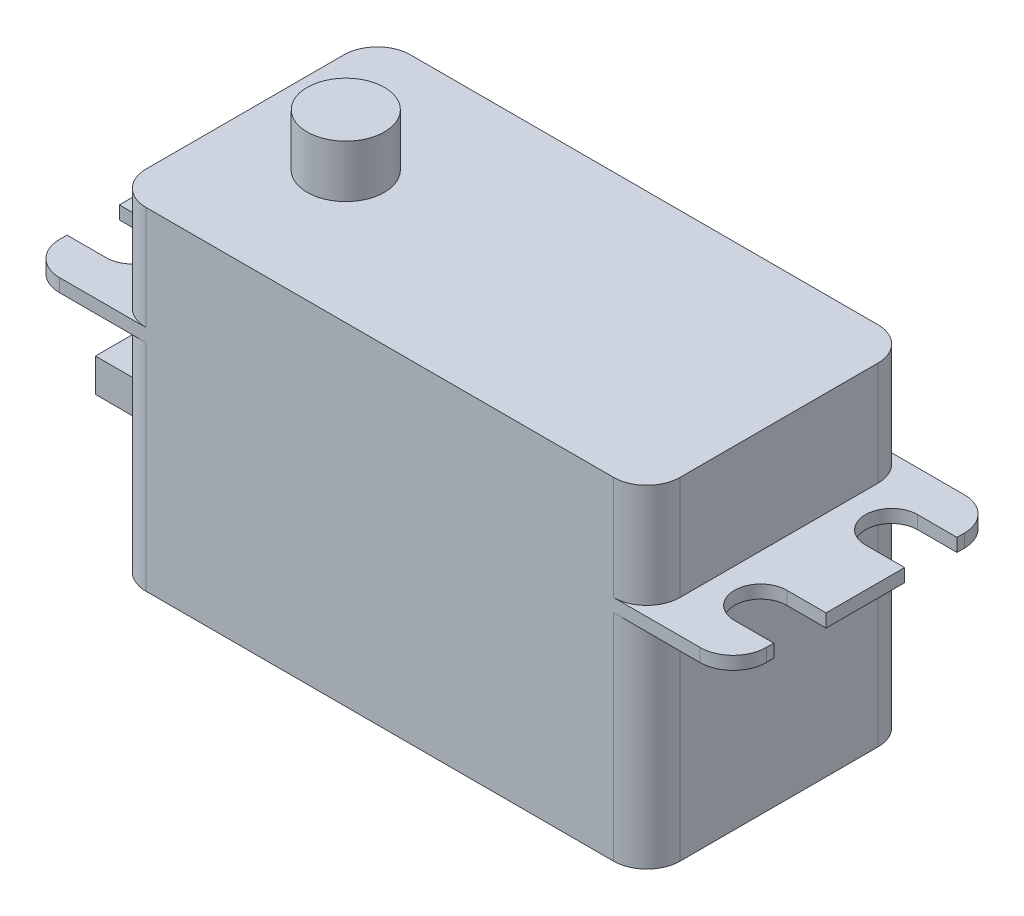
SolidWorks part; units mm, degrees
ref_plane "Front Plane" through (0, 0, 0) normal (0, 0, 1) x (1, 0, 0)
ref_plane "Top Plane" through (0, 0, 0) normal (0, 1, 0) x (1, 0, 0)
ref_plane "Right Plane" through (0, 0, 0) normal (1, 0, 0) x (0, 0, -1)
sketch "Sketch1" plane through (0, 0, 0) normal (0, 1, 0) x (1, 0, 0)
  line L0 (-16.17, 0) -> (16.17, 0) construction
  line L1 (-24.46, -10.1) -> (24.46, -10.1)
  line L2 (-27, -7.56) -> (-27, 7.56)
  line L3 (-24.46, 10.1) -> (24.46, 10.1)
  line L4 (27, -7.56) -> (27, 7.56)
  line L5 (-27, -10.1) -> (27, 10.1) construction
  line L6 (-27, 10.1) -> (27, -10.1) construction
  line L7 (0, -11.11) -> (0, 11.11) construction
  line L8 (24, 3) -> (27, 3)
  line L9 (24, 7) -> (27, 7)
  line L10 (27, 7) -> (27, 3)
  line L11 (24, -3) -> (27, -3)
  line L12 (24, -7) -> (27, -7)
  line L13 (27, -7) -> (27, -3)
  line L14 (-24, 7) -> (-27, 7)
  line L15 (-24, 3) -> (-27, 3)
  line L16 (-27, 3) -> (-27, 7)
  line L17 (-24, -7) -> (-27, -7)
  line L18 (-24, -3) -> (-27, -3)
  line L19 (-27, -3) -> (-27, -7)
  arc A0 (24, 7) -> (24, 3) centre (24, 5) ccw
  arc A1 (24, -7) -> (24, -3) centre (24, -5) cw
  arc A2 (-24, -7) -> (-24, -3) centre (-24, -5) ccw
  arc A3 (-24, 7) -> (-24, 3) centre (-24, 5) cw
  arc A4 (-24.46, -10.1) -> (-27, -7.56) centre (-24.46, -7.56) cw
  arc A5 (24.46, -10.1) -> (27, -7.56) centre (24.46, -7.56) ccw
  arc A6 (24.46, 10.1) -> (27, 7.56) centre (24.46, 7.56) cw
  arc A7 (-27, 7.56) -> (-24.46, 10.1) centre (-24.46, 7.56) cw
  point P0 (0, 0)
  dimension "D3" = 4
  dimension "D6" = 2.54
  dimension "D1" = 54
  dimension "D2" = 20.2
  dimension "D4" = 48
  dimension "D5" = 10
extrude "Boss-Extrude1" add sketch "Sketch1" along normal blind 1 contours A7 L2 L14 A3 L15 L18 A2 L17 A4 L1 A5 L4 L12 A1 L11 L8 A0 L9 A6 L3 region at (0, 0, 0)
sketch "Sketch3" plane through (0, 1, 0) normal (0, 1, 0) x (1, 0, 0)
  line L1 (-17.86, -10.1) -> (17.86, -10.1)
  line L2 (-20.4, -7.56) -> (-20.4, 7.56)
  line L3 (-17.86, 10.1) -> (17.86, 10.1)
  line L4 (20.4, -7.56) -> (20.4, 7.56)
  line L5 (-20.4, -10.1) -> (20.4, 10.1) construction
  line L6 (-20.4, 10.1) -> (20.4, -10.1) construction
  arc A0 (-17.86, -10.1) -> (-20.4, -7.56) centre (-17.86, -7.56) cw
  arc A1 (17.86, -10.1) -> (20.4, -7.56) centre (17.86, -7.56) ccw
  arc A2 (17.86, 10.1) -> (20.4, 7.56) centre (17.86, 7.56) cw
  arc A3 (-20.4, 7.56) -> (-17.86, 10.1) centre (-17.86, 7.56) cw
  point P0 (0, 0)
  dimension "D3" = 2.54
  dimension "D1" = 40.8
  dimension "D2" = 20.2
extrude "Boss-Extrude2" add sketch "Sketch3" along normal blind 7.95
sketch "Sketch4" plane through (0, 0, 0) normal (0, -1, 0) x (1, 0, 0)
  line L1 (-17.86, -10.1) -> (17.86, -10.1)
  line L2 (-20.4, -7.56) -> (-20.4, 7.56)
  line L3 (-17.86, 10.1) -> (17.86, 10.1)
  line L4 (20.4, -7.56) -> (20.4, 7.56)
  line L5 (-20.4, -10.1) -> (20.4, 10.1) construction
  line L6 (-20.4, 10.1) -> (20.4, -10.1) construction
  arc A0 (-17.86, -10.1) -> (-20.4, -7.56) centre (-17.86, -7.56) cw
  arc A1 (17.86, -10.1) -> (20.4, -7.56) centre (17.86, -7.56) ccw
  arc A2 (17.86, 10.1) -> (20.4, 7.56) centre (17.86, 7.56) cw
  arc A3 (-20.4, 7.56) -> (-17.86, 10.1) centre (-17.86, 7.56) cw
  point P0 (0, 0)
  dimension "D3" = 2.54
  dimension "D1" = 20.2
  dimension "D2" = 40.8
extrude "Boss-Extrude3" add sketch "Sketch4" along normal blind 16.45
sketch "Sketch5" plane through (-20.4, 0, 0) normal (-1, 0, 0) x (0, 0, 1)
  line L0 (-0.8843, -9.5287) -> (-0.8843, -11.2259)
  line L1 (-3.81, -11.6473) -> (3.81, -11.6473)
  line L2 (-3.81, -11.6473) -> (-3.81, -9.1073)
  line L3 (-3.81, -9.1073) -> (3.81, -9.1073)
  line L4 (3.81, -11.6473) -> (3.81, -9.1073)
  line L5 (-3.4243, -9.5287) -> (-1.6557, -9.5287)
  line L6 (-3.4243, -9.5287) -> (-3.4243, -11.2259)
  line L7 (-3.4243, -11.2259) -> (-1.6557, -11.2259)
  line L8 (-1.6557, -9.5287) -> (-1.6557, -11.2259)
  line L9 (-0.8843, -9.5287) -> (0.8843, -9.5287)
  line L10 (0.8843, -9.5287) -> (0.8843, -11.2259)
  line L11 (-0.8843, -11.2259) -> (0.8843, -11.2259)
  line L12 (1.6557, -9.5287) -> (1.6557, -11.2259)
  line L13 (1.6557, -9.5287) -> (3.4243, -9.5287)
  line L14 (3.4243, -9.5287) -> (3.4243, -11.2259)
  line L15 (1.6557, -11.2259) -> (3.4243, -11.2259)
  point P8 (0, -11.6473)
  point P18 (-3.4243, -10.3773)
  point P19 (-3.81, -10.3773)
  point P20 (0, -11.2259)
  dimension "D2" = 2.54
  dimension "D3" = 2.54
  dimension "D4" = 7.62
  dimension "D1" = 3
extrude "Boss-Extrude4" add sketch "Sketch5" along normal blind 7.62
sketch "Sketch6" plane through (0, 8.95, 0) normal (0, 1, 0) x (1, 0, 0)
  circle A0 centre (-12.7, 0) radius 2.95
  dimension "D1" = 5.9
  dimension "D2" = 12.7
extrude "Boss-Extrude5" add sketch "Sketch6" along normal blind 4
other "CPoint1"
ref_axis "Axis1" through (-38.02, -11.2259, -3.4243) along (1, 0, 0)
other "CPoint2"
ref_axis "Axis2" through (-38.02, -11.2259, -0.8843) along (1, 0, 0)
other "CPoint3"
ref_axis "Axis3" through (-38.02, -11.2259, 1.6557) along (1, 0, 0)
equation "\"Bodytube_OD\" = 6.17in"
equation "\"Bodytube_ID\" = 5.998in"
equation "\"Motor_OD\" = 4in"
equation "\"Fwd_Tube_Length\" = 40in"
equation "\"Mid_Tube_Length\" = 1in"
equation "\"Aft_Section_Length\"= 39in"
equation "\"AB_Coupler_OD_Length\"= 1in"
equation "\"AB_Coupling_Section_Length\"= 0.375in"
equation "\"AB_Coupler_Length\"= \"AB_Coupler_OD_Length\" + \"AB_Coupling_Section_Length\" * 2"
equation "\"Cutout_Angle\" = 80"
equation "\"AB_Paddle_Height\" = 0.375in"
equation "\"AB_Coupler_Num_Screws\"= 6"
equation "\"Num_Cutouts\" = 3"
equation "\"AB_Coupler_OD\"= 6.17in"
equation "\"AB_Coupler_ID\"= 5.75in"
equation "\"AB_Coupler_Surface_Diameter\"= 5.998in"
equation "\"AB_Coupling_Screw_Diameter\"= 0.1065in"
equation "\"AB_Central_Bushing_Length\" = .75in"
equation "\"Lead_Screw_Dist\" = 2.25in"
equation "\"Lead_Screw_Diam\" = 11mm"
equation "\"Paddle_Pin_Offset\" = .25in"
equation "\"Paddle_Pin_Radius\" = 2.25in"
equation "\"Paddle_Gear_OD\" = 3.2in"
equation "\"Drive_Gear_OD\" = 1.7in"
equation "\"Fwd_BKHD_From_Top\" = 18in"
equation "\"Fin_Thickness\"= .118in"
equation "\"Guiderail_Cutout_Diameter\"= 1.5in"
equation "\"DB9_Hole_Dist\" = 25mm"
equation "\"Airbrakes_Wire_Hole_Dia\" = .25in"
equation "\"Airbrakes_Wire_Hole_Dist\" = 1.1in"
equation "\"Servo_Gear_Offset\" = 0.5in"
equation "\"D2@Sketch6\"=\"Servo_Gear_Offset\""
